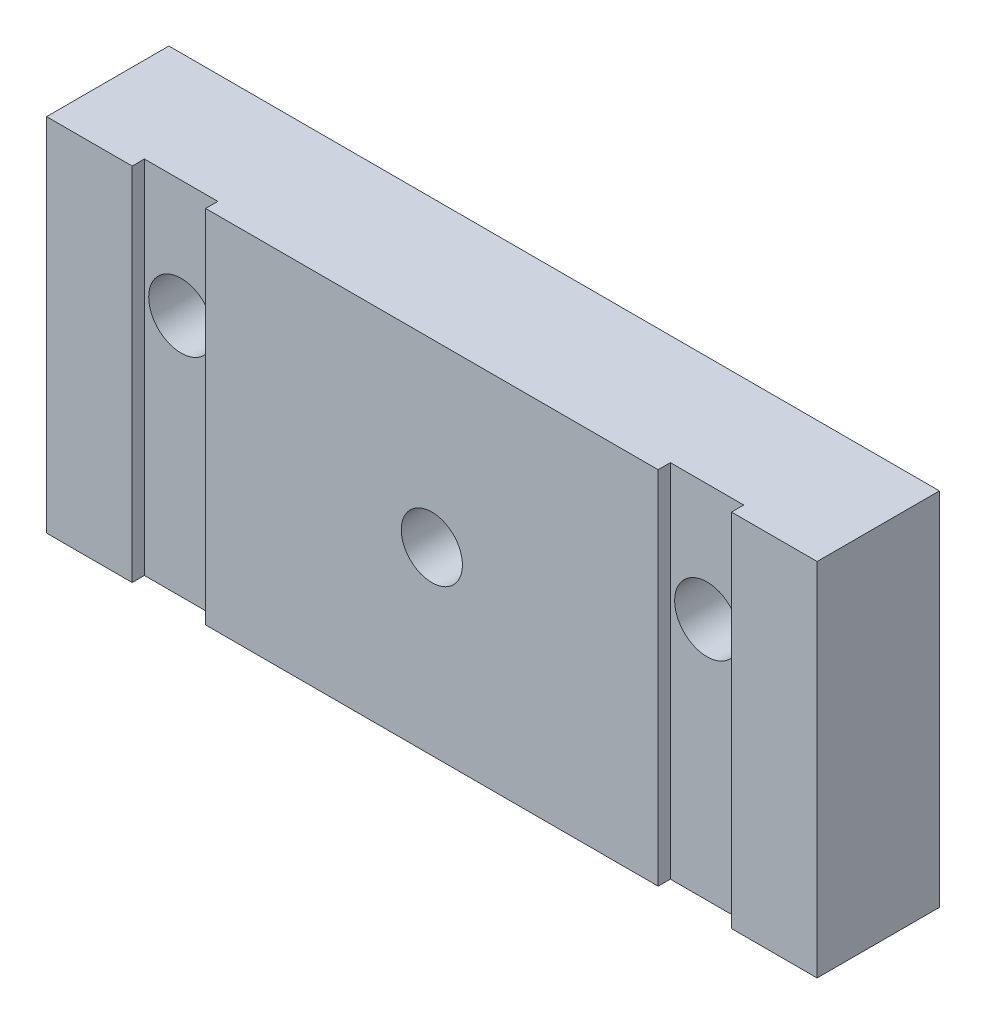
SolidWorks part; units mm, degrees
ref_plane "Front Plane" through (0, 0, 0) normal (0, 0, 1) x (1, 0, 0)
ref_plane "Top Plane" through (0, 0, 0) normal (0, 1, 0) x (1, 0, 0)
ref_plane "Right Plane" through (0, 0, 0) normal (1, 0, 0) x (0, 0, -1)
sketch "Sketch1" plane through (0, 0, 0) normal (0, 0, 1) x (1, 0, 0)
  line L1 (-10, -30) -> (53, -30) construction
  line L2 (-10, -30) -> (-10, 0) construction
  line L3 (-10, 0) -> (53, 0) construction
  line L4 (53, -30) -> (53, 0) construction
  line L5 (-10, -8.4042) -> (53, -8.4042)
  line L6 (-10, -8.4042) -> (-10, -41.0051)
  line L7 (-10, -41.0051) -> (53, -41.0051)
  line L8 (53, -8.4042) -> (53, -41.0051)
extrude "Boss-Extrude1" add sketch "Sketch1" along normal blind 10
sketch "Sketch2" plane through (0, 0, 10) normal (0, 0, 1) x (1, 0, 0)
  circle A0 centre (21.5, -23.15) radius 2.5 construction
  circle A1 centre (21.5, -23.15) radius 2.5
extrude "Cut-Extrude1" cut sketch "Sketch2" against normal through all contours A1
sketch "Sketch3" plane through (0, 0, 0) normal (0, 0, -1) x (-1, 0, 0)
  circle A0 centre (0, -18) radius 2.65 construction
  circle A1 centre (0, -18) radius 2.65
  circle A2 centre (-43, -18) radius 2.65 construction
  circle A3 centre (-43, -18) radius 2.65
extrude "Cut-Extrude2" cut sketch "Sketch3" against normal through all
sketch "Sketch4" plane through (0, 0, 10) normal (0, 0, 1) x (1, 0, 0)
  line L1 (-10, -37.8958) -> (53, -37.8958)
  line L2 (-10, -37.8958) -> (-10, -8.4042)
  line L3 (-10, -8.4042) -> (53, -8.4042)
  line L4 (53, -37.8958) -> (53, -8.4042)
  line L5 (-10, -37.8958) -> (53, -8.4042) construction
  line L6 (-10, -8.4042) -> (53, -37.8958) construction
  point P0 (21.5, -23.15)
extrude "Cut-Extrude3" cut sketch "Sketch4" against normal blind 10 flip side to cut
sketch "Sketch5" plane through (0, -37.8958, 0) normal (0, -1, 0) x (1, 0, 0)
  line L0 (-10, 10) -> (53, 10) construction
  line L13 (-10, 5) -> (53, 5) construction
  line L14 (-10, 0) -> (-10, 10) construction
  line L15 (53, 0) -> (53, 10) construction
  line L16 (-10, 19.6551) -> (-10, 10)
  line L17 (53, 19.6551) -> (-10, 19.6551)
  line L18 (53, 10) -> (53, 19.6551)
  line L19 (46, 10) -> (53, 10)
  line L20 (46, 9) -> (46, 10)
  line L21 (40, 9) -> (46, 9)
  line L22 (40, 10) -> (40, 9)
  line L23 (3, 10) -> (40, 10)
  line L24 (3, 9) -> (3, 10)
  line L25 (-3, 9) -> (3, 9)
  line L26 (-3, 10) -> (-3, 9)
  line L27 (-10, 10) -> (-3, 10)
  dimension "D1" = 1
  dimension "D2" = 6
  dimension "D3" = 7
extrude "Cut-Extrude5" cut sketch "Sketch5" against normal through all contours L17 L16 L27 L26 L25 L24 L23 L22 L21 L20 L19 L18
